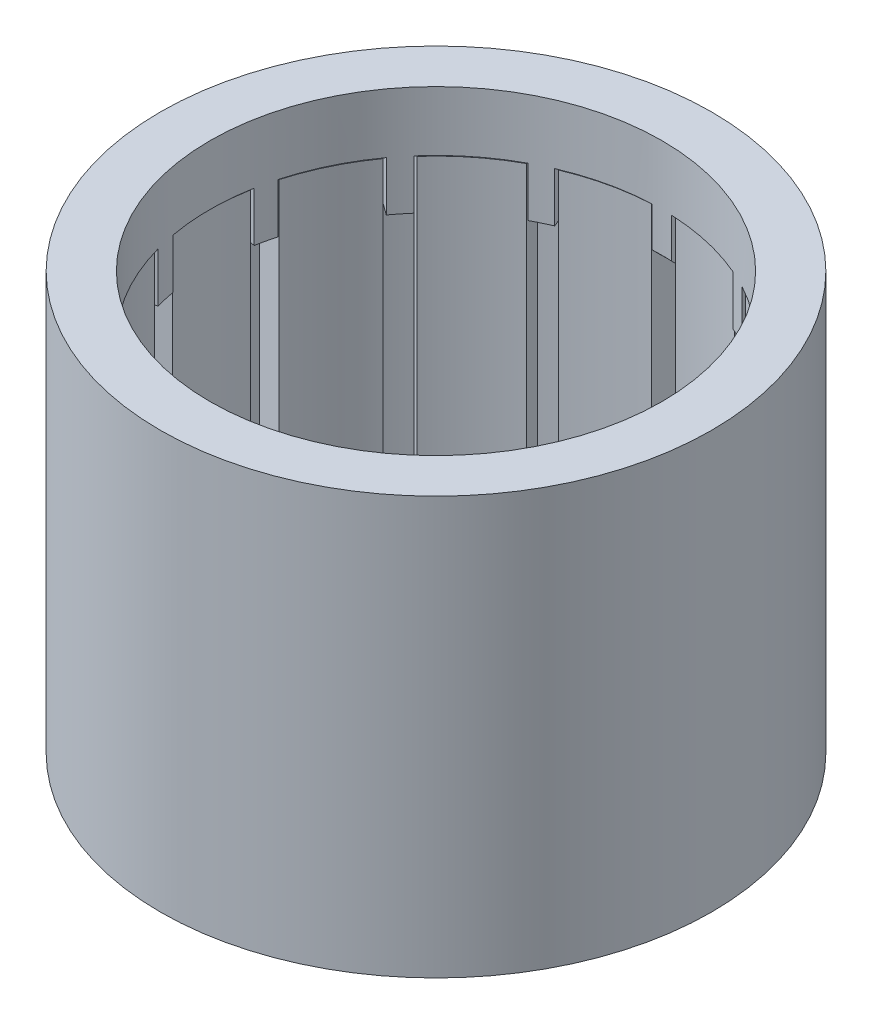
SolidWorks part; units mm, degrees
material "6061-T6 (SS)"
ref_plane "Front Plane" through (0, 0, 0) normal (0, 0, 1) x (1, 0, 0)
ref_plane "Top Plane" through (0, 0, 0) normal (0, 1, 0) x (1, 0, 0)
ref_plane "Right Plane" through (0, 0, 0) normal (1, 0, 0) x (0, 0, -1)
sketch "Sketch2" plane through (0, 0, 0) normal (1, 0, 0) x (0, 0, -1)
  line L0 (0, 0) -> (0, 12.2143) construction
  line L1 (12.975, 0) -> (13.875, 0)
  line L2 (13.875, 0) -> (13.875, 21)
  line L3 (13.875, 21) -> (11.375, 21)
  line L4 (11.375, 21) -> (11.375, 18)
  line L5 (11.375, 18) -> (12.975, 18)
  line L6 (12.975, 18) -> (12.975, 0)
  dimension "D1" = 0.9
  dimension "D2" = 21
  dimension "D3" = 27.75
  dimension "D4" = 18
  dimension "D5" = 2.5
revolve "Revolve1" add sketch "Sketch2" angle 360 about L0
sketch "Sketch3" plane through (0, 18, 0) normal (0, -1, 0) x (1, 0, 0)
  line L0 (0.5, -11.364) -> (0.5703, -12.9625)
  line L1 (-0.5, -11.364) -> (-0.5703, -12.9625)
  arc A0 (-0.5, -11.364) -> (0.5, -11.364) centre (0, 0) ccw
  circle A1 centre (0, 0) radius 11.375 construction
  circle A2 centre (0, 0) radius 12.975 construction
  arc A3 (-0.5703, -12.9625) -> (0.5703, -12.9625) centre (0, 0) ccw
  point P11 (0, -11.375)
  dimension "D1" = 1
extrude "Boss-Extrude1" add sketch "Sketch3" along normal offset from surface (2.5 mm away) 15.5 up to face at (0, 0, -13.875)
chamfer "Chamfer1" distance 0.5 angle 45 1 edges at (0, 15.5, -11.375)
pattern_circular "CirPattern1" count 14 over 360 about axis through (0, 0, 0) along (0, -1, 0) of "Boss-Extrude1"
sketch "Sketch4" plane through (0, 18, 0) normal (0, -1, 0) x (1, 0, 0)
  line L2 (-6.1787, -11.2956) -> (-5.5163, -10.0621)
  line L3 (-6.1787, -11.2956) -> (-5.5163, -10.0621)
  line L4 (-8.5823, -7.6171) -> (-9.6375, -8.5372)
  line L5 (-8.5823, -7.6171) -> (-9.6375, -8.5372)
  arc A2 (-8.5823, -7.6171) -> (-5.5163, -10.0621) centre (0, 0) ccw
  arc A3 (-8.5823, -7.6171) -> (-5.5163, -10.0621) centre (0, 0) ccw
  arc A4 (-9.6375, -8.5372) -> (-6.1787, -11.2956) centre (0, 0) ccw
  arc A6 (-9.6375, -8.5372) -> (-6.1787, -11.2956) centre (0, 0) ccw
  dimension "D1" = 0.1
extrude "Boss-Extrude2" add sketch "Sketch4" along normal offset from surface (17.4 mm away) 0.5 from offset 0.1 separate body up to face at (0, 0, -13.875)
pattern_circular "CirPattern2" count 14 over 360 about axis through (0, 0, 0) along (0, -1, 0) of bodies 104
